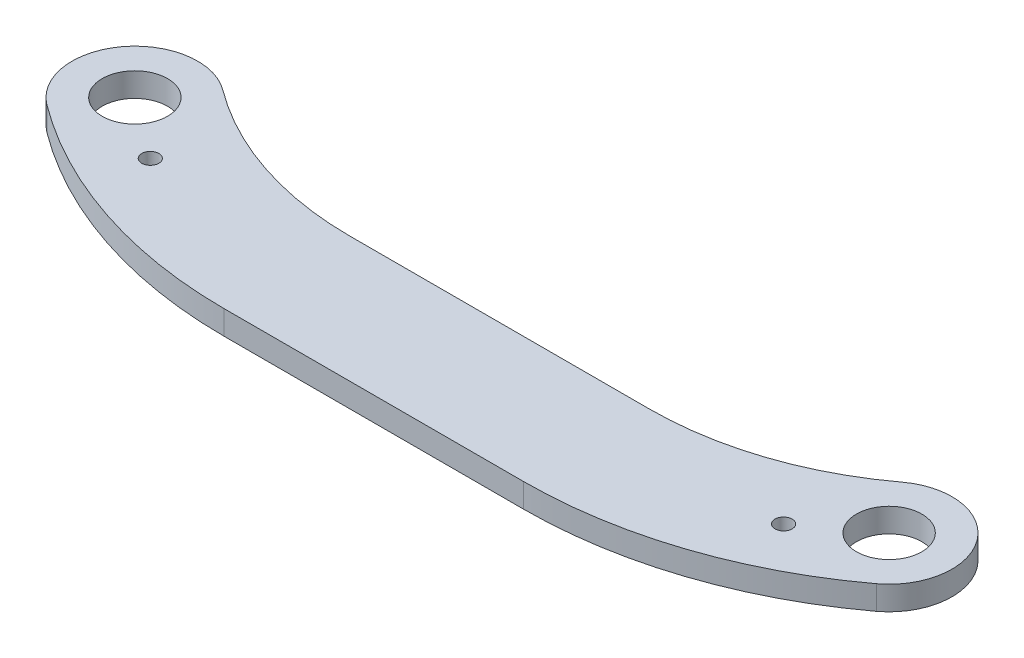
SolidWorks part; units mm, degrees
material "AISI 1020"
ref_plane "Plano frontal" through (0, 0, 0) normal (0, 0, 1) x (1, 0, 0)
ref_plane "Plano superior" through (0, 0, 0) normal (0, 1, 0) x (1, 0, 0)
ref_plane "Plano direito" through (0, 0, 0) normal (1, 0, 0) x (0, 0, -1)
sketch "Esboço1" plane through (0, 0, 0) normal (0, 1, 0) x (1, 0, 0)
  line L0 (-150, 0) -> (150, 0) construction
  line L1 (0, 0) -> (0, -5) construction
  line L2 (-59.5, -5) -> (59.5, -5)
  line L3 (-59.5, -55) -> (59.5, -55)
  line L4 (0, -5) -> (0, -55) construction
  line L5 (-125.94, -17.92) -> (125.94, -17.92) construction
  circle A0 centre (-150, 0) radius 13
  arc A2 (-135.0664, 20.0496) -> (-164.9336, -20.0496) centre (-150, 0) ccw
  arc A8 (-59.5, -5) -> (-135.0664, 20.0496) centre (-59.5, 121.5042) cw
  arc A9 (-59.5, -55) -> (-164.9336, -20.0496) centre (-59.5, 121.5042) cw
  circle A10 centre (150, 0) radius 13
  arc A11 (164.9336, -20.0496) -> (135.0664, 20.0496) centre (150, 0) ccw
  arc A12 (59.5, -5) -> (135.0664, 20.0496) centre (59.5, 121.5042) ccw
  arc A13 (164.9336, -20.0496) -> (59.5, -55) centre (59.5, 121.5042) cw
  circle A14 centre (-125.94, -17.92) radius 3.4
  circle A15 centre (125.94, -17.92) radius 3.4
  dimension "D2" = 26
  dimension "D4" = 119
  dimension "D6" = 50
  dimension "D7" = 26
  dimension "D8" = 50
  dimension "D11" = 6.8
  dimension "D1" = 300
  dimension "D3" = 5
  dimension "D5" = 50
  dimension "D9" = 251.88
  dimension "D10" = 12.92
base flange "Flange-base1" sketch "Esboço1" thickness 9.53 reverse thickness direction no parameters "D1"=0.7366
sketch "Curva-Linhas1" [suppressed] plane through (0, 0, 0) normal (0, 1, 0) x (1, 0, 0)
sketch "Caixa delimitadora1" [suppressed] plane through (0, 0, 0) normal (0, 1, 0) x (1, 0, 0)
sheet metal parameters "Chapa metálica1" thickness 9.53 parameters "D1"=0.7366
flat pattern "Padrão-Plano1" [suppressed]
sketch "Curva-Linhas2" plane through (0, 0, 0) normal (0, 1, 0) x (1, 0, 0)
sketch3d "Caixa delimitadora2" [suppressed]
  line L0 (-234.5, -96.5042, 0) -> (115.5, -96.5042, 0) construction
  line L1 (-234.5, -176.5042, 0) -> (115.5, -176.5042, 0) construction
  line L2 (-234.5, -96.5042, 0) -> (-234.5, -176.5042, 0) construction
  line L3 (115.5, -96.5042, 0) -> (115.5, -176.5042, 0) construction
